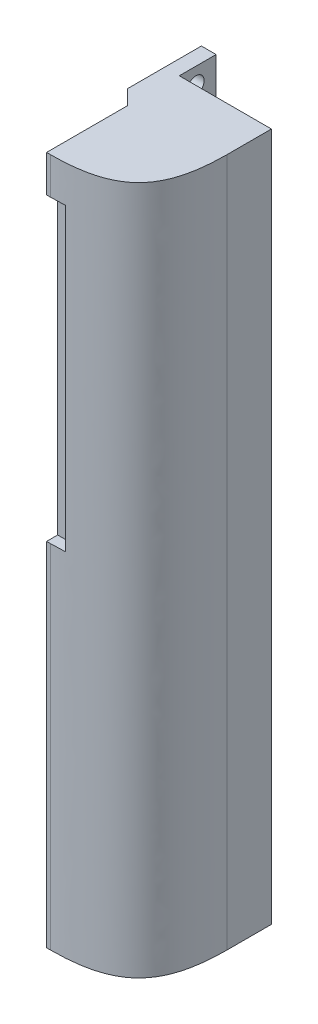
SolidWorks part; units mm, degrees
ref_plane "Front Plane" through (0, 0, 0) normal (0, 0, 1) x (1, 0, 0)
ref_plane "Top Plane" through (0, 0, 0) normal (0, 1, 0) x (1, 0, 0)
ref_plane "Right Plane" through (0, 0, 0) normal (1, 0, 0) x (0, 0, -1)
sketch "Sketch1" plane through (0, 0, 0) normal (0, 1, 0) x (1, 0, 0)
  line L1 (0, 0) -> (25, 0)
  line L2 (0, 0) -> (0, 36)
  line L3 (0, 36) -> (25, 36)
  line L4 (25, 0) -> (25, 36)
  dimension "D1" = 25
  dimension "D2" = 36
extrude "Boss-Extrude1" add sketch "Sketch1" along normal blind 186.9
fillet "Fillet1" radius 24 1 edges at (25, 93.45, 0) conic rho 0.55
ref_plane "Plane1" through (0, 0, 0) normal (0, 0, -1) x (-1, 0, 0)
sketch "Sketch2" plane through (0, 0, 0) normal (0, 0, -1) x (-1, 0, 0)
  line L1 (0, 176.9) -> (-5, 176.9)
  line L2 (0, 176.9) -> (0, 95.5)
  line L3 (0, 95.5) -> (-5, 95.5)
  line L4 (-5, 176.9) -> (-5, 95.5)
  line L5 (-1, 186.9) -> (-25, 186.9) construction
  point P8 (0, 0)
  dimension "D1" = 10
  dimension "D2" = 81.4
  dimension "D3" = 5
extrude "Cut-Extrude1" cut sketch "Sketch2" along normal blind 3
sketch "Sketch6" plane through (0, 0, -36) normal (0, 0, -1) x (-1, 0, 0)
  line L0 (0, 186.9) -> (0, 0) construction
  line L1 (0, 186.9) -> (4, 186.9)
  line L2 (0, 186.9) -> (0, 176.9)
  line L3 (0, 176.9) -> (4, 176.9)
  line L4 (4, 186.9) -> (4, 176.9)
  line L5 (0, 66.9) -> (4, 66.9)
  line L6 (0, 66.9) -> (0, 76.9)
  line L7 (0, 76.9) -> (4, 76.9)
  line L8 (4, 66.9) -> (4, 76.9)
  line L9 (-25, 186.9) -> (0, 186.9) construction
  dimension "D1" = 10
  dimension "D2" = 4
  dimension "D3" = 4
  dimension "D4" = 10
  dimension "D5" = 120
extrude "Boss-Extrude3" add sketch "Sketch6" against normal blind 10 and the other way blind 10
sketch "Sketch7" plane through (-4, 0, 0) normal (-1, 0, 0) x (0, 0, 1)
  line L0 (-36, 176.9) -> (-36, 76.9) construction
  line L1 (-46, 186.9) -> (-26, 186.9) construction
  line L2 (-46, 66.9) -> (-26, 66.9) construction
  line L3 (-36, 66.9) -> (-36, 0) construction
  circle A0 centre (-40.5, 182.4) radius 2.25
  circle A1 centre (-40.5, 71.4) radius 2.25
  dimension "D3" = 4.5
  dimension "D6" = 4.5
  dimension "D1" = 4.5
  dimension "D2" = 4.5
  dimension "D4" = 4.5
  dimension "D5" = 4.5
extrude "Cut-Extrude2" cut sketch "Sketch7" against normal up to next
chamfer "Chamfer1" distance 4 angle 45 2 edges at (0, 181.9, -26) (0, 71.9, -26)
